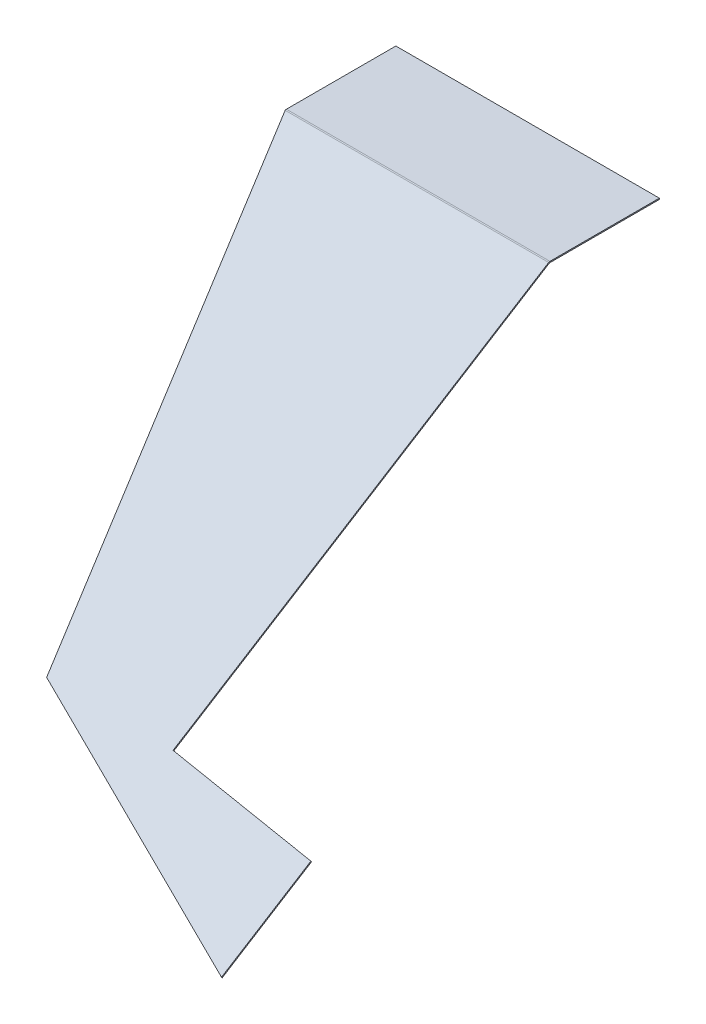
SolidWorks part; units mm, degrees
note: The reader was unsure of these and kept them because the rebuilt part matched: flange length of "Edge-Flange1".
ref_plane "Front Plane" through (0, 0, 0) normal (0, 0, 1) x (1, 0, 0)
ref_plane "Top Plane" through (0, 0, 0) normal (0, 1, 0) x (1, 0, 0)
ref_plane "Right Plane" through (0, 0, 0) normal (1, 0, 0) x (0, 0, -1)
sketch "Sketch1" plane through (0, 0, 0) normal (0, 1, 0) x (1, 0, 0)
  line L1 (-90, -37.5) -> (90, -37.5)
  line L2 (-90, -37.5) -> (-90, 37.5)
  line L3 (-90, 37.5) -> (90, 37.5)
  line L4 (90, -37.5) -> (90, 37.5)
  line L5 (-90, -37.5) -> (90, 37.5) construction
  line L6 (-90, 37.5) -> (90, -37.5) construction
  point P0 (0, 0)
  dimension "D1" = 180
  dimension "D2" = 75
sheet metal parameters "Sheet-Metal1" thickness 0.8 parameters "D1"=0.8
base flange "Base-Flange1" sketch "Sketch1" thickness 0.8 reverse thickness direction no parameters "D1"=0.8
edge flange "Edge-Flange1" sketch "Sketch4" flange angle 148 flange length 303 flange position material outside bend radius 0.8 thickness 0.8 parameters "D6"=10
sketch "Sketch4" plane through (0, -0.8, 37.5) normal (0, -0.848, -0.5299) x (1, 0, 0)
  line L1 (90, 0) -> (-90, 0) construction
  line L2 (-90, 0) -> (-90, 302.7706)
  line L3 (-90, 302.7706) -> (90, 302.7706)
  line L4 (90, 302.7706) -> (90, 0)
  line L5 (90, 0) -> (-90, 0)
bend "EdgeBend1" bend radius 0.8 bend angle 32 parameters "D5"=1
sketch "Sketch5" plane through (0, 16.9555, 10.595) normal (0, 0.848, 0.5299) x (1, 0, 0)
  line L0 (-90, -32.4551) -> (11.5802, -360.6079)
  line L1 (-90, -334.9963) -> (-90, -32.4551) construction
  line L2 (-90, -32.4551) -> (-238.9104, -331.9862)
  line L3 (-238.9104, -331.9862) -> (11.5802, -360.6079)
  dimension "D1" = 17.2
extrude "Cut-Extrude1" cut sketch "Sketch5" against normal blind 10
sketch "Sketch6" plane through (0, 16.9555, 10.595) normal (0, 0.848, 0.5299) x (1, 0, 0)
  line L0 (3.6521, -334.9963) -> (195.4991, -420.3806)
  line L1 (195.4991, -420.3806) -> (195.4991, -348.3837)
  line L2 (195.4991, -348.3837) -> (90, -334.9963)
  line L3 (90, -334.9963) -> (3.6521, -334.9963)
base flange "Tab1" sketch "Sketch6" thickness 0.8 reverse thickness direction no parameters "D1"=0.8
flat pattern "Flat-Pattern1" [suppressed]
sketch "Bend-Lines1" plane through (0, 0, 0) normal (0, 1, 0) x (-1, 0, 0)
bend of the flat pattern "Flatten-<EdgeBend1>1"
